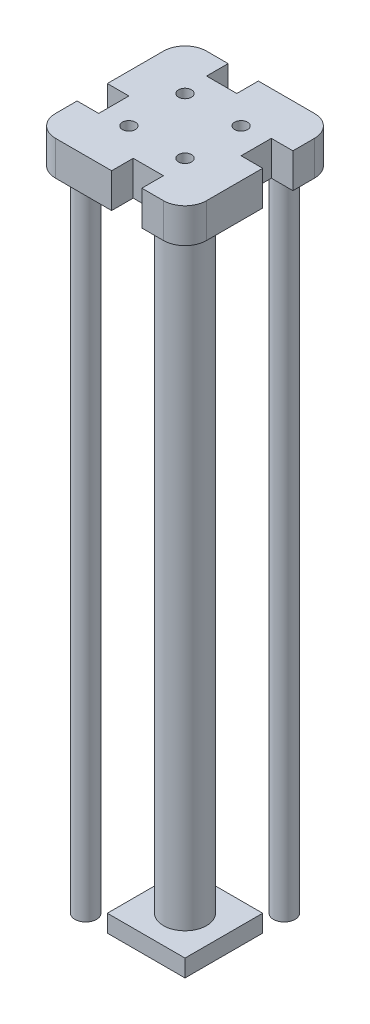
SolidWorks part; units mm, degrees
ref_plane "Front Plane" through (0, 0, 0) normal (0, 0, 1) x (1, 0, 0)
ref_plane "Top Plane" through (0, 0, 0) normal (0, 1, 0) x (1, 0, 0)
ref_plane "Right Plane" through (0, 0, 0) normal (1, 0, 0) x (0, 0, -1)
sketch "Sketch1" plane through (0, 0, 0) normal (0, 1, 0) x (1, 0, 0)
  line L1 (0, 0) -> (35, 0)
  line L2 (0, 0) -> (0, 35)
  line L3 (0, 35) -> (35, 35)
  line L4 (35, 0) -> (35, 35)
  dimension "D1" = 35
  dimension "D2" = 35
extrude "Boss-Extrude1" add sketch "Sketch1" along normal blind 8
sketch "Sketch2" plane through (0, 0, 0) normal (0, -1, 0) x (1, 0, 0)
  line L0 (0, 0) -> (35, 0) construction
  line L1 (18, 0) -> (25, 0)
  line L2 (18, 0) -> (18, -5)
  line L3 (18, -5) -> (25, -5)
  line L4 (25, 0) -> (25, -5)
  line L5 (35, -35) -> (0, -35) construction
  line L6 (10, -35) -> (17, -35)
  line L7 (10, -35) -> (10, -30)
  line L8 (10, -30) -> (17, -30)
  line L9 (17, -35) -> (17, -30)
  line L10 (0, -35) -> (0, 0) construction
  line L11 (0, -10) -> (5, -10)
  line L12 (0, -10) -> (0, -17)
  line L13 (0, -17) -> (5, -17)
  line L14 (5, -10) -> (5, -17)
  line L15 (35, 0) -> (35, -35) construction
  line L16 (35, -18) -> (30, -18)
  line L17 (35, -18) -> (35, -25)
  line L18 (35, -25) -> (30, -25)
  line L19 (30, -18) -> (30, -25)
  circle A0 centre (6, -6) radius 2.5
  circle A1 centre (29, -6) radius 4
  circle A2 centre (6, -29) radius 4
  circle A3 centre (29, -29) radius 2.5
  circle A4 centre (17.5, -17.5) radius 5
  circle A5 centre (11, -11) radius 1.5
  circle A6 centre (24, -11) radius 1.5
  circle A7 centre (24, -24) radius 1.5
  circle A8 centre (11, -24) radius 1.5
  point P45 (17.5, 0)
  point P46 (35, -17.5)
  line M26 (0, 0) -> (0, -35)
  line M27 (0, -35) -> (35, -35)
  line M28 (35, -35) -> (35, 0)
  line M29 (35, 0) -> (0, 0)
  dimension "D7" = 5
  dimension "D8" = 5
  dimension "D9" = 8
  dimension "D10" = 8
  dimension "D11" = 10
  dimension "D12" = 3
  dimension "D13" = 3
  dimension "D14" = 3
  dimension "D15" = 3
  dimension "D1" = 5
  dimension "D2" = 7
  dimension "D3" = 10
  dimension "D4" = 10
  dimension "D5" = 10
  dimension "D6" = 10
  dimension "D16" = 6
  dimension "D17" = 6
  dimension "D18" = 6
  dimension "D19" = 6
  dimension "D20" = 6
  dimension "D21" = 6
  dimension "D22" = 6
  dimension "D23" = 11
  dimension "D24" = 6
  dimension "D25" = 11
extrude "Cut-Extrude1" cut sketch "Sketch2" against normal through all contours L16 L19 L18 M28 | L9 L8 L7 M27 | L14 L11 L13 M26 | L4 L2 L3 M29 | A5 | A6 | A8 | A7 region at (21.5, 0, -2.5) region at (2.5, 0, -13.5) region at (32.5, 0, -21.5) region at (13.5, 0, -32.5) region at (11, 0, -11) region at (24, 0, -11) region at (24, 0, -24) region at (11, 0, -24)
extrude "Cut-Extrude2" cut sketch "Sketch2<5>" against normal blind 4 contours A2 | A1 | A5 region at (6, 0, -29)
sketch "Sketch2<5>" plane through (0, 0, 0) normal (0, -1, 0) x (1, 0, 0) same geometry as "Sketch2"
extrude "Boss-Extrude2" add sketch "Sketch2<7>" along normal blind 150 contours A4 | A3 | A0 region at (29, 0, -29) region at (17.5, 0, -17.5)
sketch "Sketch2<7>" plane through (0, 0, 0) normal (0, -1, 0) x (1, 0, 0) same geometry as "Sketch2"
sketch "Sketch3" plane through (0, -150, 0) normal (0, -1, 0) x (-1, 0, 0)
  line L0 (0, 10) -> (0, 0) construction
  line L1 (-8.5, 8.5) -> (-26.5, 8.5)
  line L2 (-8.5, 8.5) -> (-8.5, 26.5)
  line L3 (-8.5, 26.5) -> (-26.5, 26.5)
  line L4 (-26.5, 8.5) -> (-26.5, 26.5)
  line L5 (-25, 0) -> (-35, 0) construction
  line L6 (-35, 0) -> (-35, 18) construction
  line L7 (-35, 35) -> (-17, 35) construction
  dimension "D1" = 8.5
  dimension "D2" = 8.5
  dimension "D3" = 8.5
  dimension "D4" = 8.5
extrude "Boss-Extrude3" add sketch "Sketch3" along normal blind 4
fillet "Fillet1" radius 5 4 edges at (35, 4, -35) (0, 4, -35) (0, 4, 0) (35, 4, 0)
